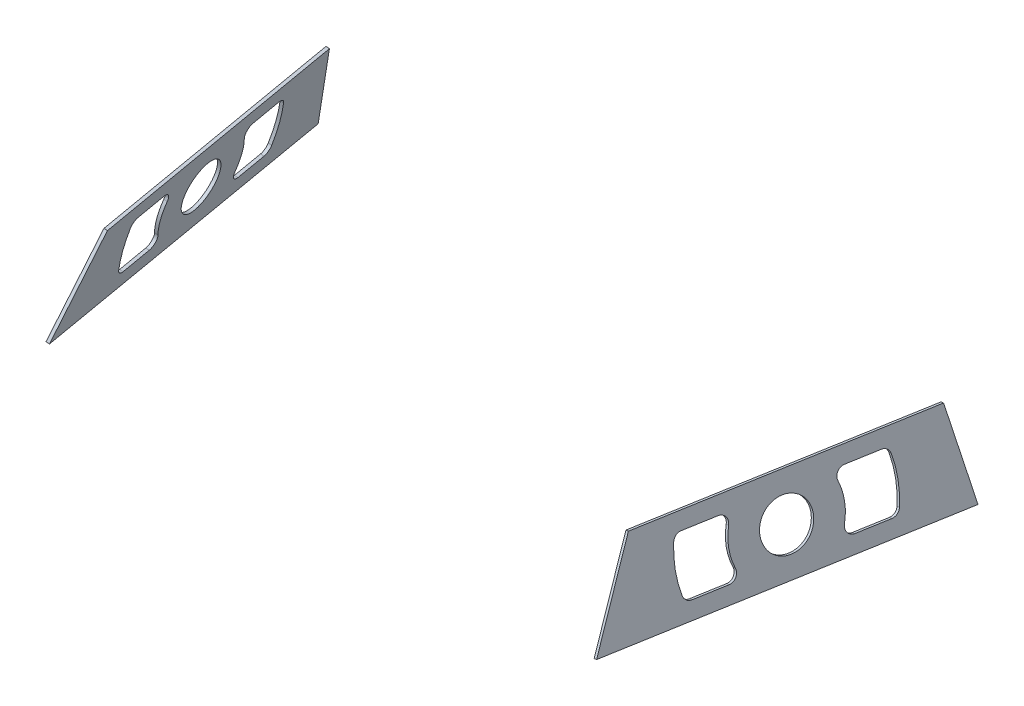
SolidWorks part; units mm, degrees
material "AISI 4130 Steel, normalized at 870C"
ref_plane "Front Plane" through (0, 0, 0) normal (0, 0, 1) x (1, 0, 0)
ref_plane "Top Plane" through (0, 0, 0) normal (0, 1, 0) x (1, 0, 0)
ref_plane "Right Plane" through (0, 0, 0) normal (1, 0, 0) x (0, 0, -1)
ref_plane "Plane1" through (-623.1255, 157.9159, 108.0618) normal (-0.9559, 0.2423, 0.1658) x (0.1607, -0.0407, 0.9862)
sketch "Sketch1" plane through (-623.1255, 157.9159, 108.0618) normal (-0.9559, 0.2423, 0.1658) x (0.1607, -0.0407, 0.9862)
  line L0 (1410.8518, 806.0855) -> (1403.247, 750.7175)
  line L1 (1403.247, 750.7175) -> (1617.0419, 759.6995)
  line L2 (1617.0419, 759.6995) -> (1587.5198, 813.5078)
  line L3 (1587.5198, 813.5078) -> (1410.8518, 806.0855)
  line L4 (1409.8147, 798.5353) -> (1404.284, 758.2677) construction
  line L5 (1591.5455, 806.1703) -> (1613.0162, 767.037) construction
  line L6 (1409.8147, 798.5353) -> (1433.754, 799.5411) construction
  line L7 (1581.1847, 765.6997) -> (1613.0162, 767.037) construction
  dimension "D1" = 55
  dimension "D2" = 7.5
extrude "Boss-Extrude1" add sketch "Sketch1" along normal blind 2
sketch "Sketch2" plane through (-623.1255, 157.9159, 108.0618) normal (-0.9559, 0.2423, 0.1658) x (0.1607, -0.0407, 0.9862)
  circle A0 centre (1568.5033, 796.1943) radius 2.75 construction
  circle A1 centre (1568.5033, 796.1943) radius 2.75
  circle A2 centre (1580.3122, 774.671) radius 2.75 construction
  circle A3 centre (1580.3122, 774.671) radius 2.75
  circle A4 centre (1433.9515, 790.5414) radius 2.75 construction
  circle A5 centre (1433.9515, 790.5414) radius 2.75
  circle A6 centre (1430.9096, 768.3942) radius 2.75 construction
  circle A7 centre (1430.9096, 768.3942) radius 2.75
extrude "Cut-Extrude1" [suppressed] cut sketch "Sketch2" against normal through all both and the other way through all
sketch "Sketch3" plane through (-623.1255, 157.9159, 108.0618) normal (-0.9559, 0.2423, 0.1658) x (0.1607, -0.0407, 0.9862)
  line L0 (1407.0494, 778.4015) -> (1602.2808, 786.6037) construction
  line L1 (1410.8518, 806.0855) -> (1403.247, 750.7175) construction
  line L2 (1617.0419, 759.6995) -> (1587.5198, 813.5078) construction
  line L3 (1499.1858, 809.7966) -> (1510.1445, 755.2085) construction
  line L4 (1587.5198, 813.5078) -> (1410.8518, 806.0855) construction
  line L5 (1403.247, 750.7175) -> (1617.0419, 759.6995) construction
  circle A0 centre (1504.6651, 782.5026) radius 15
  dimension "D1" = 30
extrude "Cut-Extrude4" cut sketch "Sketch3" along normal blind 2 contours A0
sketch "Sketch4" plane through (-625.0374, 158.4004, 108.3934) normal (-0.9559, 0.2423, 0.1658) x (0.1607, -0.0407, 0.9862)
  line L0 (1468.557, 798.501) -> (1447.8252, 797.63)
  line L1 (1470.1319, 763.5363) -> (1449.361, 762.6637)
  line L2 (1539.3104, 801.4735) -> (1560.0422, 802.3445)
  line L3 (1540.6738, 766.4999) -> (1561.4447, 767.3726)
  line L4 (1587.5198, 813.5078) -> (1410.8518, 806.0855) construction
  line L6 (1403.247, 750.7175) -> (1617.0419, 759.6995) construction
  line L7 (1468.557, 798.501) -> (1539.3104, 801.4735) construction
  line L8 (1470.1319, 763.5363) -> (1540.6738, 766.4999) construction
  arc A1 (1443.111, 793.5024) -> (1444.3241, 766.3555) centre (1504.662, 782.6522) ccw
  arc A2 (1535.6903, 772.9831) -> (1534.8725, 794.6345) centre (1504.662, 782.6522) ccw
  arc A3 (1566.1542, 771.4739) -> (1565.086, 798.6269) centre (1504.662, 782.6522) ccw
  arc A4 (1561.4447, 767.3726) -> (1566.1542, 771.4739) centre (1561.2349, 772.3682) ccw
  arc A5 (1560.0422, 802.3445) -> (1565.086, 798.6269) centre (1560.2521, 797.3489) cw
  arc A9 (1449.361, 762.6637) -> (1444.3241, 766.3555) centre (1449.1511, 767.6593) cw
  arc A11 (1447.8252, 797.63) -> (1443.111, 793.5024) centre (1448.0351, 792.6344) ccw
  arc A12 (1473.5529, 792.0583) -> (1474.554, 770.4146) centre (1504.662, 782.6522) ccw
  arc A13 (1470.1319, 763.5363) -> (1474.554, 770.4146) centre (1469.922, 768.5319) ccw
  arc A14 (1473.5529, 792.0583) -> (1468.557, 798.501) centre (1468.7669, 793.5054) ccw
  arc A15 (1535.6903, 772.9831) -> (1540.6738, 766.4999) centre (1540.4639, 771.4955) ccw
  arc A16 (1534.8725, 794.6345) -> (1539.3104, 801.4735) centre (1539.5203, 796.478) cw
  point P12 (1468.2932, 792.6344)
  point P14 (1470.2947, 767.6593)
  point P15 (1469.4086, 795.4946)
  point P16 (1565.3062, 767.5348)
  point P30 (1445.4996, 762.5014)
  point P36 (1443.9432, 797.4669)
  point P37 (0, 0)
  point P38 (0, 0)
  point P39 (0, 0)
  point P44 (0, 0)
  point P45 (0, 0)
  point P46 (0, 0)
  dimension "D1" = 32.5
  dimension "D2" = 125
  dimension "D5" = 5
  dimension "D6" = 32.5
  dimension "D8" = 5
  dimension "D7" = 5
  dimension "D9" = 5
  dimension "D10" = 5
  dimension "D3" = 10
  dimension "D4" = 10
extrude "Cut-Extrude5" cut sketch "Sketch4" against normal through all both and the other way through all
sketch "Sketch5" plane through (-625.0374, 158.4004, 108.3934) normal (-0.9559, 0.2423, 0.1658) x (0.1607, -0.0407, 0.9862)
  circle A0 centre (1504.6614, 782.68) radius 20 construction
  circle A1 centre (1504.6614, 782.68) radius 20
  circle A2 centre (1504.662, 782.6522) radius 14.5 construction
  circle A3 centre (1504.662, 782.6522) radius 14.5
split line "Split Line1" [suppressed]
mirror "Mirror2" about plane through (0, 0, 0) normal (1, 0, 0) of bodies 104
